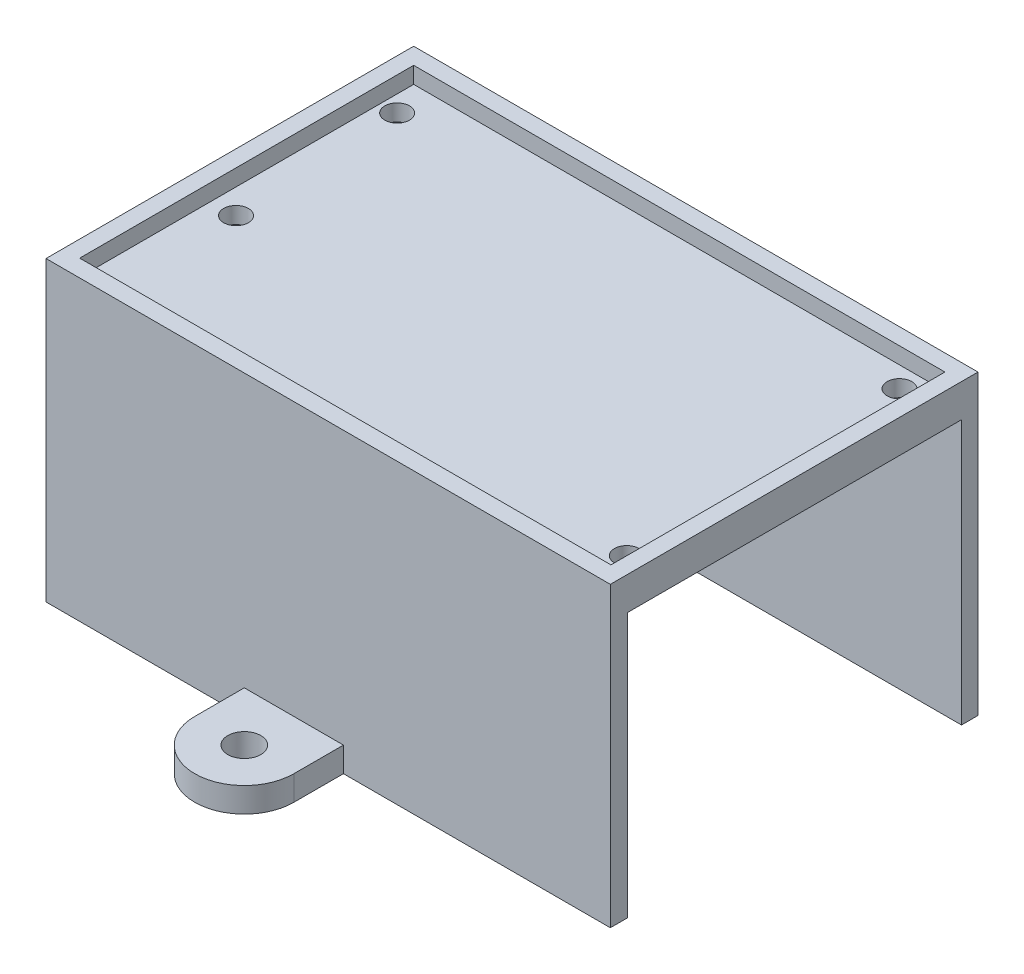
SolidWorks part; units mm, degrees
ref_plane "Front Plane" through (0, 0, 0) normal (0, 0, 1) x (1, 0, 0)
ref_plane "Top Plane" through (0, 0, 0) normal (0, 1, 0) x (1, 0, 0)
ref_plane "Right Plane" through (0, 0, 0) normal (1, 0, 0) x (0, 0, -1)
sketch "Sketch1" plane through (0, 0, 0) normal (0, 1, 0) x (1, 0, 0)
  line L0 (-31.4611, 14.9769) -> (-31.4611, -29.5231)
  line L1 (-29.4611, 12.9769) -> (34.8389, 12.9769)
  line L2 (-29.4611, 12.9769) -> (-29.4611, -27.5231)
  line L3 (-29.4611, -27.5231) -> (34.8389, -27.5231)
  line L4 (34.8389, 12.9769) -> (34.8389, -27.5231)
  line L5 (-31.4611, -29.5231) -> (36.8389, -29.5231)
  line L6 (36.8389, 14.9769) -> (36.8389, -29.5231)
  line L7 (-31.4611, 14.9769) -> (36.8389, 14.9769)
  circle A0 centre (-26.4611, -11.5231) radius 1.5
  circle A1 centre (31.8389, 10.4769) radius 1.5
  circle A2 centre (32.8389, -23.5231) radius 1.5
  circle A3 centre (-27.4611, 8.9769) radius 1.5
  dimension "D6" = 3
  dimension "D7" = 3
  dimension "D14" = 3
  dimension "D15" = 3
  dimension "D1" = 64.3
  dimension "D2" = 40.5
  dimension "D4" = 3
  dimension "D5" = 16
  dimension "D8" = 4
  dimension "D9" = 2
  dimension "D10" = 3
  dimension "D11" = 2.5
  dimension "D12" = 4
  dimension "D13" = 2
  dimension "D3" = 2
extrude "Boss-Extrude1" add sketch "Sketch1" along normal blind 2 contours L4 L1 L2 L3 A3 A2 A1 A0 region at (2.6889, 0, 7.3101)
extrude "Boss-Extrude2" add sketch "Sketch1<3>" along normal blind 4 contours L7 L0 L5 L6 L1 L4 L3 L2 region at (2.6889, 0, -14.1617)
sketch "Sketch1<3>" plane through (0, 0, 0) normal (0, 1, 0) x (1, 0, 0) same geometry as "Sketch1"
sketch "Sketch3" plane through (0, 0, 0) normal (0, -1, 0) x (1, 0, 0)
  line L0 (36.8389, -14.9769) -> (36.8389, 29.5231) construction
  line L1 (-31.4611, -14.9769) -> (-29.4611, -14.9769)
  line L2 (-31.4611, -14.9769) -> (-31.4611, 29.5231)
  line L3 (-31.4611, 29.5231) -> (-29.4611, 29.5231)
  line L4 (-29.4611, -14.9769) -> (-29.4611, 29.5231)
  line L5 (-31.4611, -14.9769) -> (36.8389, -14.9769)
  line L6 (-31.4611, -14.9769) -> (-31.4611, -12.9775)
  line L7 (-31.4611, -12.9775) -> (36.8389, -12.9775)
  line L8 (36.8389, -14.9769) -> (36.8389, -12.9775)
  line L10 (-31.4611, 29.5231) -> (36.8389, 29.5231)
  line L11 (-31.4611, 29.5231) -> (-31.4611, 27.447)
  line L12 (-31.4611, 27.447) -> (36.8389, 27.447)
  line L13 (36.8389, 29.5231) -> (36.8389, 27.447)
  line M5 (-31.4611, -14.9769) -> (36.8389, -14.9769)
  line M6 (36.8389, -14.9769) -> (36.8389, 29.5231)
  line M7 (36.8389, 29.5231) -> (-31.4611, 29.5231)
  line M8 (-31.4611, 29.5231) -> (-31.4611, -14.9769)
  dimension "D1" = 2
extrude "Boss-Extrude3" add sketch "Sketch3" along normal blind 32 and the other way blind 4 contours L4 L1 L2 L3 M8 | L12 M8 M6 M7 | L7 L2 M5 M6 | L2 L1 L4 L3 region at (3.6889, 0, -13.9772) region at (3.6889, 0, 28.485)
sketch "Sketch5" plane through (0, -32, 0) normal (0, -1, 0) x (1, 0, 0)
  line L5 (-29.4611, 7.2347) -> (31.8375, 7.2347)
  line L6 (-29.4611, -12.9775) -> (-29.4611, 27.447) construction
  line L8 (36.8389, 27.447) -> (-29.4611, 27.447) construction
  line L9 (4.5389, 43.5992) -> (-7.4611, 43.5992)
  line L10 (4.5389, 43.5992) -> (4.5389, 27.447)
  line L11 (4.5389, 27.447) -> (-7.4611, 27.447)
  line L12 (-7.4611, 43.5992) -> (-7.4611, 27.447)
  line L13 (4.5389, 43.5992) -> (-7.4611, 27.447) construction
  line L14 (4.5389, 27.447) -> (-7.4611, 43.5992) construction
  line L15 (36.8389, 29.5231) -> (-31.4611, 29.5231) construction
  line L16 (4.5389, -12.9775) -> (-7.4611, -29.1297) construction
  line L17 (4.5389, -29.1297) -> (-7.4611, -12.9775) construction
  line L18 (-7.4611, -29.1297) -> (-7.4611, -12.9775)
  line L19 (4.5389, -12.9775) -> (-7.4611, -12.9775)
  line L20 (4.5389, -29.1297) -> (4.5389, -12.9775)
  line L21 (4.5389, -29.1297) -> (-7.4611, -29.1297)
  circle A2 centre (-1.4611, 35.5231) radius 2
  circle A3 centre (-1.4611, 35.5231) radius 6
  circle A4 centre (-1.4611, -21.0536) radius 6
  circle A5 centre (-1.4611, -21.0536) radius 2
  line M3 (36.8389, 29.5231) -> (-31.4611, 29.5231)
  line M4 (-31.4611, 29.5231) -> (-31.4611, -14.9769)
  line M5 (-31.4611, -14.9769) -> (36.8389, -14.9769)
  line M7 (36.8389, -12.9775) -> (-29.4611, -12.9775)
  dimension "D5" = 4
  dimension "D6" = 12
  dimension "D7" = 12
  dimension "D8" = 6
  dimension "D9" = 30
extrude "Boss-Extrude4" add sketch "Sketch5" against normal blind 3 contours M4 | M4 | A3 L12 M3 | A3 L10 M3 | A3 A2 | L20 L18 M5 M7 | L18 A4 L20 M5 | A4 A5 region at (-1.4611, -32, -13.9772) region at (-1.4611, -32, -14.9904) region at (2.6615, -32, 31.4005) region at (3.1987, -32, 30.8633) region at (-6.1209, -32, 30.8633) region at (-1.4611, -32, -15.2233)
